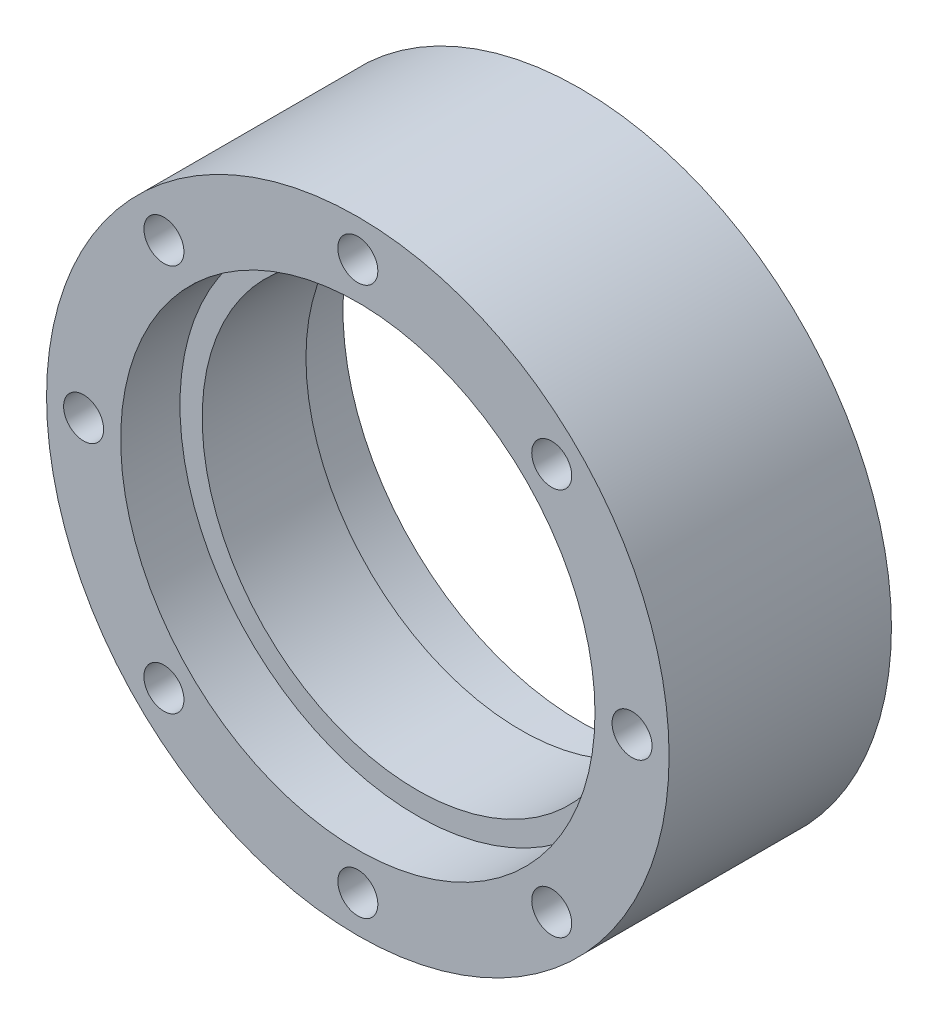
SolidWorks part; units mm, degrees
ref_plane "Front Plane" through (0, 0, 0) normal (0, 0, 1) x (1, 0, 0)
ref_plane "Top Plane" through (0, 0, 0) normal (0, 1, 0) x (1, 0, 0)
ref_plane "Right Plane" through (0, 0, 0) normal (1, 0, 0) x (0, 0, -1)
ref_axis "Z" through (0, 0, 8.25) along (0, 0, -1)
sketch "Sketch1" plane through (0, 0, 0) normal (0, 0, 1) x (1, 0, 0)
  circle A0 centre (0, 0) radius 21
  circle A1 centre (0, 0) radius 14.5
  dimension "D1" = 29
  dimension "D2" = 42
extrude "MainBody" add sketch "Sketch1" along normal blind 7.5 and the other way blind 7.5
sketch "Sketch2" plane through (0, 0, 7.5) normal (0, 0, 1) x (1, 0, 0)
  circle A0 centre (0, 0) radius 16
  dimension "D1" = 32
extrude "Cut-Extrude1" cut sketch "Sketch2" against normal blind 4
mirror "Mirror1" about plane through (0, 0, 0) normal (0, 0, 1) of "Cut-Extrude1"
sketch "Sketch3" plane through (0, 0, 0) normal (0, 0, 1) x (1, 0, 0)
  line L1 (0, 21) -> (0, 16) construction
  circle A0 centre (0, 18.5) radius 1.35
  circle A2 centre (0, 0) radius 21 construction
  circle A3 centre (0, 0) radius 16 construction
  circle A4 centre (0, 0) radius 18.5 construction
  dimension "D1" = 2.7
  dimension "D2" = 32
  dimension "D3" = 37
extrude "Cut-Extrude2" cut sketch "Sketch3" against normal through all both and the other way through all
sketch "Sketch4" plane through (0, 0, -7.5) normal (0, 0, -1) x (-1, 0, 0)
  circle A0 centre (0, 18.5) radius 2.25
  circle A1 centre (0, 18.5) radius 1.35 construction
  dimension "D1" = 4.5
extrude "Cut-Extrude4" cut sketch "Sketch4" against normal blind 2.5 and the other way through all
chamfer "Chamfer1" distance 0.1 angle 45 1 edges at (-1.35, 18.5, -5)
pattern_circular "CirPattern1" count 8 over 360 about axis through (0, 0, 8.25) along (0, 0, -1) of "Cut-Extrude2", "Cut-Extrude4", "Chamfer1"
equation "\"BearingBaseDistance\"= 7"
equation "\"BearingOD\"= 32"
equation "\"BearingHeight\"= 4"
equation "\"D1@Cut-Extrude1\"=\"BearingHeight\""
equation "\"D1@MainBody\" = \"BearingBaseDistance\" / 2 + \"BearingHeight\""
equation "\"D2@MainBody\" = \"BearingBaseDistance\" / 2 + \"BearingHeight\""
equation "\"D1@Sketch1\"=\"BearingOD\"-3"
equation "\"D1@Sketch2\"=\"BearingOD\""
equation "\"SeatsOD\"= \"BearingOD\" + 10"
equation "\"D2@Sketch1\"=\"SeatsOD\""
equation "\"D2@Sketch3\"=\"BearingOD\""
